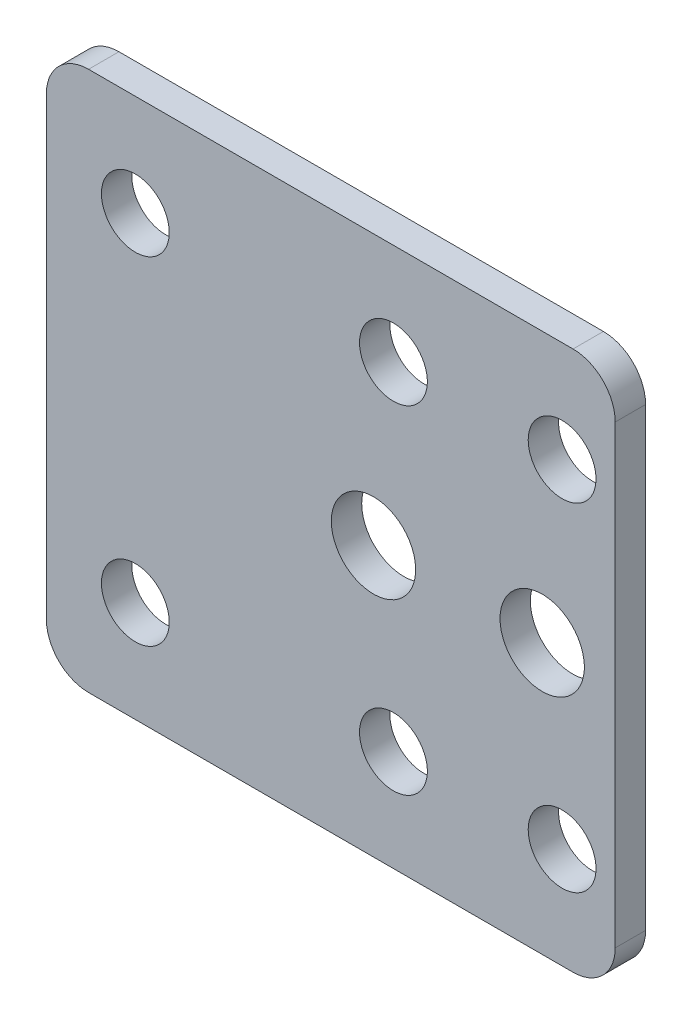
SolidWorks part; units mm, degrees
material "5052-H32"
ref_plane "Front Plane" through (0, 0, 0) normal (0, 0, 1) x (1, 0, 0)
ref_plane "Top Plane" through (0, 0, 0) normal (0, 1, 0) x (1, 0, 0)
ref_plane "Right Plane" through (0, 0, 0) normal (1, 0, 0) x (0, 0, -1)
sketch "Sketch1" plane through (0, 0, 0) normal (0, 0, 1) x (1, 0, 0)
  line L0 (-81.1185, -171.1815) -> (-107.2918, -171.1815) construction
  line L1 (-157.3185, -191.5015) -> (-81.1185, -191.5015)
  line L2 (-157.3185, -191.5015) -> (-157.3185, -150.8615)
  line L3 (-157.3185, -150.8615) -> (-81.1185, -150.8615)
  line L4 (-81.1185, -191.5015) -> (-81.1185, -150.8615)
  dimension "D1" = 40.64
  dimension "D2" = 76.2
base flange "Base-Flange1" sketch "Sketch1" thickness 2.286 reverse thickness direction yes parameters "D1"=2.9972
sketch "Sketch6" plane through (0, 0, 0) normal (0, 0, -1) x (-1, 0, 0)
  circle A0 centre (150.6232, -158.4815) radius 2.5527 construction
  circle A1 centre (150.6232, -158.4815) radius 2.5527 construction
  circle B0 centre (150.6232, -158.4815) radius 2.5527
  circle B1 centre (150.6232, -183.8815) radius 2.5527
  circle B2 centre (118.4918, -158.4815) radius 2.5527
  circle B3 centre (119.9918, -171.1815) radius 3.175
  circle B4 centre (118.4918, -183.8815) radius 2.5527
  circle B5 centre (131.1918, -158.4815) radius 2.5527
  circle B6 centre (132.6918, -171.1815) radius 3.175
  circle B7 centre (131.1918, -183.8815) radius 2.5527
  circle B8 centre (105.7918, -158.4815) radius 2.5527
  circle B9 centre (107.2918, -171.1815) radius 3.175
  circle B10 centre (105.7918, -183.8815) radius 2.5527
  circle B11 centre (93.0918, -158.4815) radius 2.5527
  circle B12 centre (94.5918, -171.1815) radius 3.175
  circle B13 centre (93.0918, -183.8815) radius 2.5527
sketch_block_instance "VersaPlanetary Side Mount 0-3 Stages-1"
sketch_block "VersaPlanetary Side Mount 0-3 Stages" parameters "D1"=5.1054, "D2"=6.35
extrude "Cut-Extrude1" cut sketch "Sketch6" against normal up to next normal cut yes
fillet "Fillet1" radius 3.175 4 edges at (-157.3185, -150.8615, 1.143) (-81.1185, -150.8615, 1.143) (-81.1185, -191.5015, 1.143) (-157.3185, -191.5015, 1.143)
sketch "Sketch7" plane through (0, 0, 2.286) normal (0, 0, 1) x (1, 0, 0)
  line L0 (-154.1435, -191.5015) -> (-84.2935, -191.5015) construction
  line L1 (-101.7927, -191.5015) -> (-48.3078, -191.5015)
  line L2 (-101.7927, -191.5015) -> (-101.7927, -149.9643)
  line L3 (-101.7927, -149.9643) -> (-48.3078, -149.9643)
  line L4 (-48.3078, -191.5015) -> (-48.3078, -149.9643)
  circle A0 centre (-107.2918, -171.1815) radius 3.175 construction
  dimension "D1" = 5.4991
extrude "Remove 3rd Stage" cut sketch "Sketch7" against normal blind 2.54 normal cut yes
fillet "Fillet2" radius 3.175 2 edges at (-101.7927, -191.5015, 1.143) (-101.7927, -150.8615, 1.143)
sketch "Sketch8" plane through (0, 0, 2.286) normal (0, 0, 1) x (1, 0, 0)
  line L1 (-114.4927, -202.5646) -> (-87.9151, -202.5646)
  line L2 (-114.4927, -202.5646) -> (-114.4927, -137.7844)
  line L3 (-114.4927, -137.7844) -> (-87.9151, -137.7844)
  line L4 (-87.9151, -202.5646) -> (-87.9151, -137.7844)
  circle A0 centre (-119.9918, -171.1815) radius 3.175 construction
  dimension "D1" = 5.4991
extrude "Remove 2nd Stage" cut sketch "Sketch8" against normal through all normal cut yes
fillet "Fillet3" radius 3.175 2 edges at (-114.4927, -191.5015, 1.143) (-114.4927, -150.8615, 1.143)
sketch "Sketch9" [suppressed] plane through (0, 0, 2.286) normal (0, 0, 1) x (1, 0, 0)
  line L1 (-125.4147, -196.4173) -> (-89.1801, -196.4173)
  line L2 (-125.4147, -196.4173) -> (-125.4147, -142.3862)
  line L3 (-125.4147, -142.3862) -> (-89.1801, -142.3862)
  line L4 (-89.1801, -196.4173) -> (-89.1801, -142.3862)
  circle A0 centre (-130.9138, -171.7346) radius 3.175 construction
  dimension "D1" = 5.4991
extrude "Cut-Extrude2" [suppressed] cut sketch "Sketch9" against normal up to next
fillet "Fillet4" [suppressed] radius 3.175
sketch "Bend-Lines1" [suppressed] plane through (0, 0, 0) normal (0, 1, 0) x (1, 0, 0)
sketch "Bounding-Box1" [suppressed] plane through (0, 0, 0) normal (0, 1, 0) x (1, 0, 0)
sheet metal parameters "Sheet-Metal1" thickness 2.286 parameters "D1"=2.9972
flat pattern "Flat-Pattern1" [suppressed]
sketch "Bend-Lines2" plane through (0, 0, 0) normal (0, 1, 0) x (1, 0, 0)
sketch "Bounding-Box2" [suppressed] plane through (0, 0, 0) normal (0, 1, 0) x (1, 0, 0)
sheet metal parameters "Sheet-Metal2" thickness 2.286 parameters "D1"=2.9972
flat pattern "Flat-Pattern1"
sketch "Bend-Lines2" plane through (0, 0, 0) normal (0, 1, 0) x (1, 0, 0)
sketch3d "Bounding-Box2" [suppressed]
  line L0 (157.3185, -192.0546, 0) -> (81.1185, -192.0546, 0) construction
  line L1 (157.3185, -151.4146, 0) -> (81.1185, -151.4146, 0) construction
  line L2 (157.3185, -192.0546, 0) -> (157.3185, -151.4146, 0) construction
  line L3 (81.1185, -192.0546, 0) -> (81.1185, -151.4146, 0) construction
sheet metal parameters "Sheet-Metal3" thickness 2.286 parameters "D1"=2.9972
flat pattern "Flat-Pattern1"
sketch "Bend-Lines2" plane through (0, 0, 0) normal (0, 1, 0) x (1, 0, 0)
sketch3d "Bounding-Box2" [suppressed]
  line L0 (157.3185, -192.0546, 0) -> (100.0147, -192.0546, 0) construction
  line L1 (157.3185, -151.4146, 0) -> (100.0147, -151.4146, 0) construction
  line L2 (157.3185, -192.0546, 0) -> (157.3185, -151.4146, 0) construction
  line L3 (100.0147, -192.0546, 0) -> (100.0147, -151.4146, 0) construction
sheet metal parameters "Sheet-Metal4" thickness 2.286 parameters "D1"=2.9972
flat pattern "Flat-Pattern1"
sketch "Bend-Lines2" plane through (0, 0, 0) normal (0, 1, 0) x (1, 0, 0)
sketch3d "Bounding-Box2" [suppressed]
  line L0 (157.3185, -191.5015, 0) -> (114.4927, -191.5015, 0) construction
  line L1 (157.3185, -150.8615, 0) -> (114.4927, -150.8615, 0) construction
  line L2 (157.3185, -191.5015, 0) -> (157.3185, -150.8615, 0) construction
  line L3 (114.4927, -191.5015, 0) -> (114.4927, -150.8615, 0) construction
sheet metal parameters "Sheet-Metal5" [suppressed] thickness 2.286 parameters "D1"=2.9972
flat pattern "Flat-Pattern1"
sketch "Bend-Lines2" plane through (0, 0, 0) normal (0, 1, 0) x (1, 0, 0)
sketch3d "Bounding-Box2" [suppressed]
  line L0 (157.3185, -192.0546, 0) -> (112.7147, -192.0546, 0) construction
  line L1 (157.3185, -151.4146, 0) -> (112.7147, -151.4146, 0) construction
  line L2 (157.3185, -192.0546, 0) -> (157.3185, -151.4146, 0) construction
  line L3 (112.7147, -192.0546, 0) -> (112.7147, -151.4146, 0) construction
